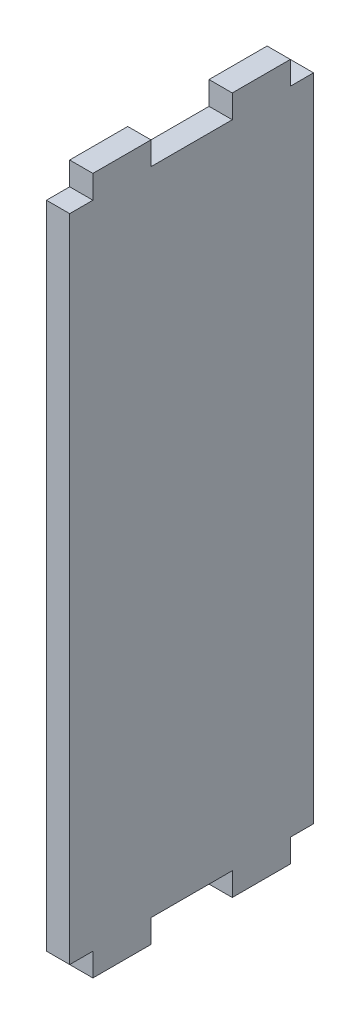
SolidWorks part; units mm, degrees
ref_plane "Front Plane" through (0, 0, 0) normal (0, 0, 1) x (1, 0, 0)
ref_plane "Top Plane" through (0, 0, 0) normal (0, 1, 0) x (1, 0, 0)
ref_plane "Right Plane" through (0, 0, 0) normal (1, 0, 0) x (0, 0, -1)
sketch "Sketch1" plane through (0, 0, 0) normal (1, 0, 0) x (0, 0, -1)
  line L0 (33.3375, 0) -> (-33.3375, 0) construction
  line L1 (-33.3375, 88.9) -> (33.3375, 88.9)
  line L2 (-33.3375, 88.9) -> (-33.3375, -88.9)
  line L3 (-33.3375, -88.9) -> (33.3375, -88.9)
  line L4 (33.3375, 88.9) -> (33.3375, -88.9)
  line L5 (26.9875, -88.9) -> (26.9875, -95.25)
  line L6 (-26.9875, 88.9) -> (-11.1125, 88.9)
  line L7 (-26.9875, 88.9) -> (-26.9875, 95.25)
  line L8 (-26.9875, 95.25) -> (-11.1125, 95.25)
  line L9 (-11.1125, 88.9) -> (-11.1125, 95.25)
  line L10 (11.1125, 88.9) -> (26.9875, 88.9)
  line L11 (11.1125, 88.9) -> (11.1125, 95.25)
  line L12 (11.1125, 95.25) -> (26.9875, 95.25)
  line L13 (26.9875, 88.9) -> (26.9875, 95.25)
  line L14 (11.1125, -95.25) -> (26.9875, -95.25)
  line L15 (11.1125, -88.9) -> (11.1125, -95.25)
  line L16 (-11.1125, -88.9) -> (-11.1125, -95.25)
  line L17 (-26.9875, -88.9) -> (-26.9875, -95.25)
  line L18 (-26.9875, -95.25) -> (-11.1125, -95.25)
  point P4 (0, 88.9)
  point P6 (33.3375, 0)
  point P17 (11.1125, 92.075)
  dimension "D1" = 66.675
  dimension "D2" = 177.8
  dimension "D3" = 6.35
  dimension "D4" = 15.875
  dimension "D5" = 22.225
  dimension "D6" = 6.35
extrude "Boss-Extrude1" add sketch "Sketch1" along normal blind 6.35 contours L0 L4 L1 L2 | L1 L13 L12 L11 | L4 L0 L2 L3 | L17 L18 L16 L3 | L3 L15 L14 L5 | L1 L9 L8 L7 | L8 L9 L6 L7 region at (0, -44.45, 0) region at (0, 44.45, 0) region at (0, 92.075, -19.05) region at (0, -92.075, -19.05) region at (0, 92.075, 19.05) region at (0, -92.075, 19.05)
